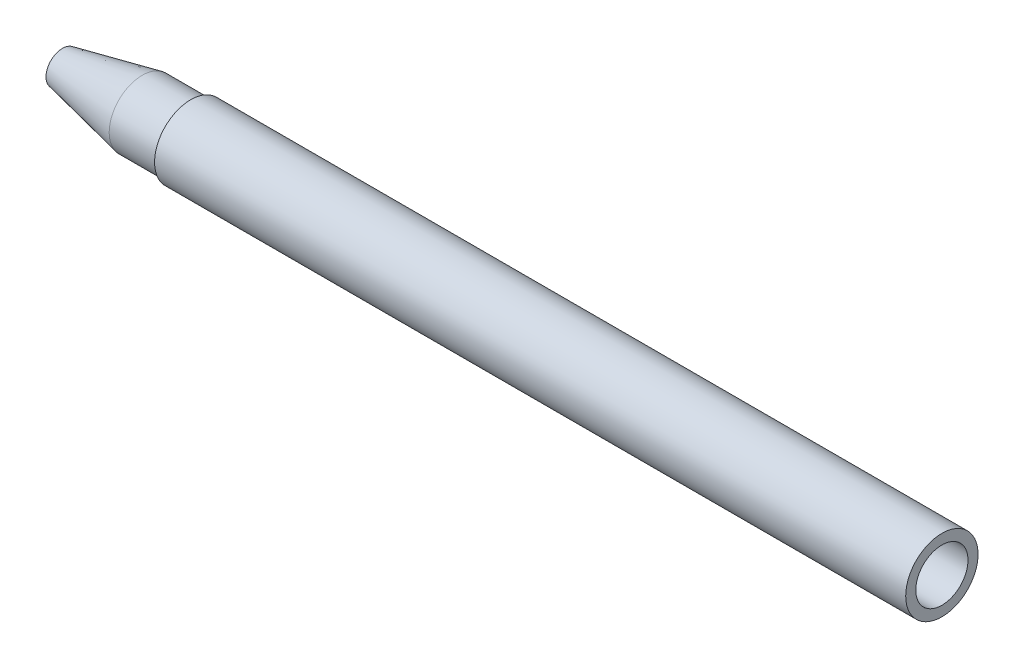
SolidWorks part; units mm, degrees
ref_plane "Front Plane" through (0, 0, 0) normal (0, 0, 1) x (1, 0, 0)
ref_plane "Top Plane" through (0, 0, 0) normal (0, 1, 0) x (1, 0, 0)
ref_plane "Right Plane" through (0, 0, 0) normal (1, 0, 0) x (0, 0, -1)
sketch "Sketch1" plane through (0, 0, 0) normal (0, 0, 1) x (1, 0, 0)
  line L0 (-51.9, 0) -> (51.9, 0)
  line L1 (51.9, 0) -> (51.9, -1.39)
  line L3 (-51.9, 0) -> (-51.9, -0.43)
  line L4 (-51.9, -0.43) -> (-58.6, -0.43)
  line L5 (-58.6, -0.43) -> (-69.63, -2.73)
  line L9 (-81.2361, -5) -> (54.8523, -5) construction
  line L10 (51.9, -1.39) -> (-58.6, -1.39)
  line L11 (-58.6, -1.39) -> (-69.63, -3.69)
  line L12 (-69.63, -3.69) -> (-69.63, -2.73)
  point P4 (0, 0)
  point P7 (-353.9719, -3.69)
  point P10 (661.7554, -1.39)
  point P11 (159.7401, -3.69)
  point P13 (-81.2361, -5)
  point P15 (54.8523, -5)
  dimension "D1" = 1.39
  dimension "D2" = 103.8
  dimension "D3" = 0.43
  dimension "D4" = 6.7
  dimension "D5" = 11.03
  dimension "D6" = 2.3
  dimension "D7" = 5
revolve "Revolve1" add sketch "Sketch1" angle 360 about L9
